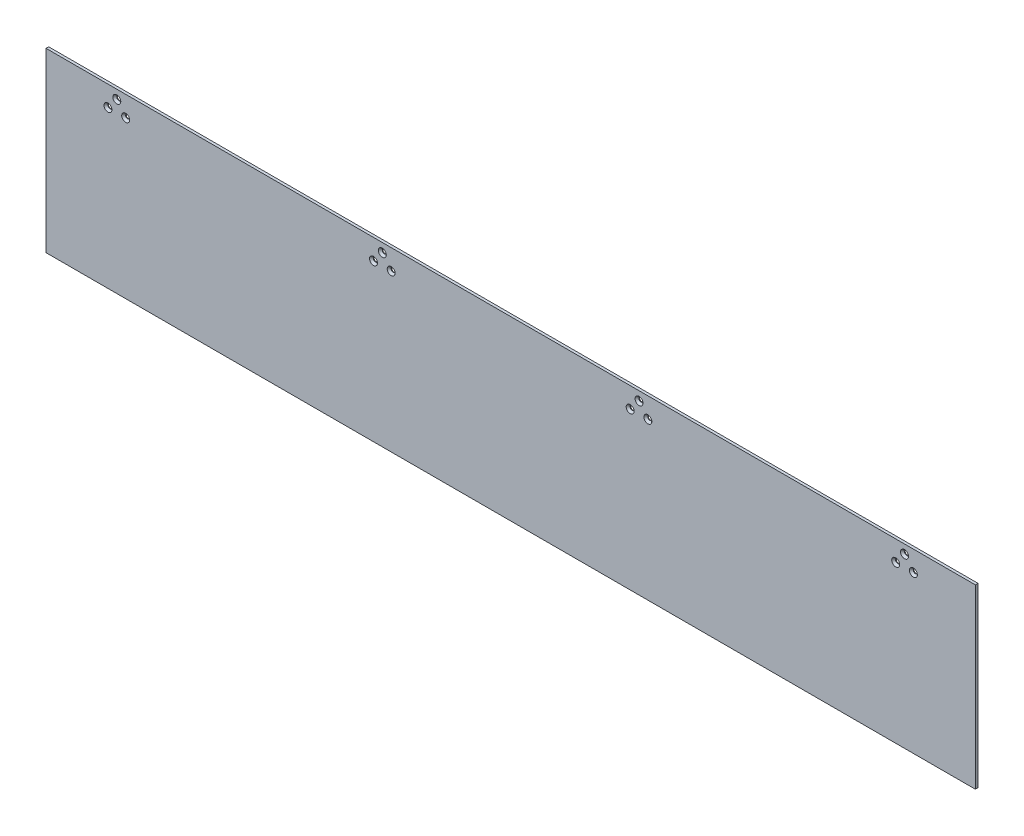
SolidWorks part; units mm, degrees
ref_plane "Front Plane" through (0, 0, 0) normal (0, 0, 1) x (1, 0, 0)
ref_plane "Top Plane" through (0, 0, 0) normal (0, 1, 0) x (1, 0, 0)
ref_plane "Right Plane" through (0, 0, 0) normal (1, 0, 0) x (0, 0, -1)
sketch "Sketch1" plane through (0, 0, 0) normal (0, 0, 1) x (1, 0, 0)
  line L1 (-525, -100) -> (525, -100)
  line L2 (-525, -100) -> (-525, 100)
  line L3 (-525, 100) -> (525, 100)
  line L4 (525, -100) -> (525, 100)
  line L5 (-525, -100) -> (525, 100) construction
  line L6 (-525, 100) -> (525, -100) construction
  point P0 (0, 0)
  dimension "D1" = 1050
  dimension "D2" = 200
extrude "Boss-Extrude1" add sketch "Sketch1" along normal blind 3 contours L2 L1 L4 L3
hole_wizard "CSK for M4 SFHCS1" positions "Sketch2" profile "Sketch3" countersink size "M4" standard "ANSI Metric" end condition through all
sketch "Sketch2" plane through (0, 0, 3) normal (0, 0, 1) x (1, 0, 0)
  line L0 (-455, 77) -> (-435, 77)
  line L2 (-525, 100) -> (525, 100) construction
  line L3 (-155, 77) -> (-135, 77)
  point P0 (-455, 77)
  point P1 (-435, 77)
  point P7 (-445, 77)
  point P18 (-155, 77)
  point P19 (-135, 77)
  point P21 (-445, 90)
  point P30 (-145, 90)
  dimension "D1" = 20
  dimension "D2" = 23
  dimension "D3" = 80
  dimension "D5" = 10
  dimension "D4" = 2
  dimension "D6" = 2
sketch "Sketch3" plane through (-455, 77, 3) normal (1, 0, 0) x (0, -1, 0)
  line L0 (0, 0) -> (0, 3)
  line L1 (0, 3) -> (2.25, 3)
  line L2 (2.25, 3) -> (2.25, 2.23)
  line L3 (2.25, 2.23) -> (4.48, 0)
  line L5 (4.48, 0) -> (0, 0)
  line L6 (-2.25, 2.23) -> (-4.48, 0) construction
  line L11 (0, -6.35) -> (0, 107.95) construction
  dimension "Thru Hole Dia." = 4.5
  dimension "Thru Hole Depth" = 3
  dimension "Near C'Sink Dia." = 8.96
  dimension "Near C'Sink Angle" = 90
mirror "Mirror1" about plane through (0, 0, 0) normal (1, 0, 0) of "CSK for M4 SFHCS1"
